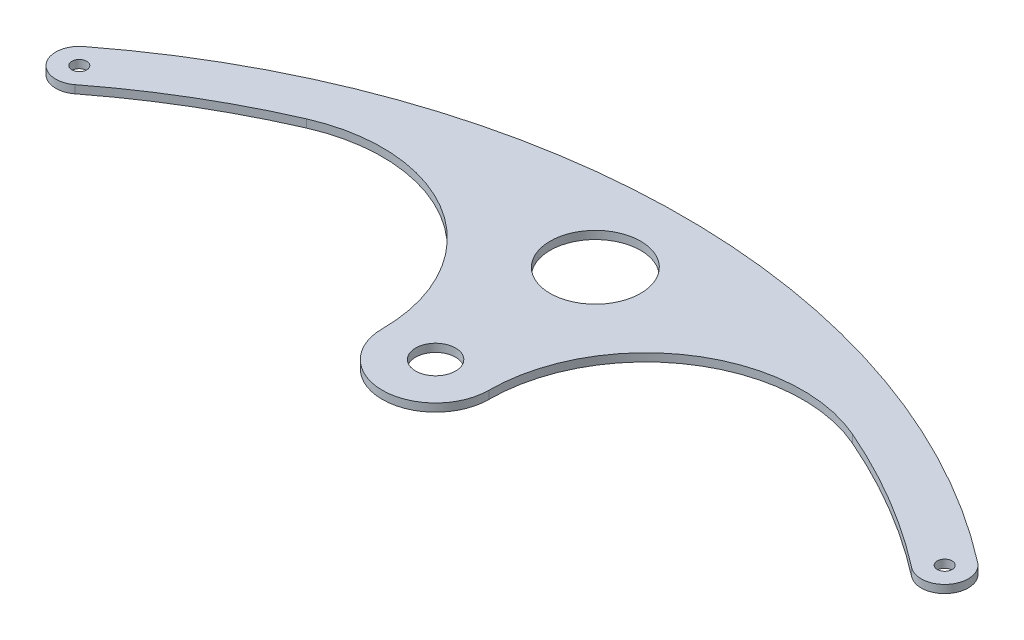
SolidWorks part; units mm, degrees
ref_plane "Front Plane" through (0, 0, 0) normal (0, 0, 1) x (1, 0, 0)
ref_plane "Top Plane" through (0, 0, 0) normal (0, 1, 0) x (1, 0, 0)
ref_plane "Right Plane" through (0, 0, 0) normal (1, 0, 0) x (0, 0, -1)
sketch "Sketch1" plane through (0, 0, 0) normal (0, 1, 0) x (1, 0, 0)
  line L0 (3.048, 4.191) -> (3.048, -6.604) construction
  line L1 (0, 0) -> (206.375, 0) construction
  line L2 (103.1875, 0) -> (103.1875, 50.9033) construction
  line L3 (47.625, 0) -> (47.625, 19.05) construction
  line L4 (60.3023, -7.112) -> (162.9473, -7.112) construction
  line L5 (60.3023, -18.2245) -> (162.9473, -18.2245) construction
  line L6 (103.1875, 0) -> (103.1875, -18.2245) construction
  circle A0 centre (0, 0) radius 1.778
  circle A1 centre (206.375, 0) radius 1.778
  arc A3 (-3.435, 4.439) -> (3.435, -4.439) centre (0, 0) ccw
  arc A4 (209.81, 4.439) -> (202.94, -4.439) centre (206.375, 0) cw
  arc A5 (202.94, -4.439) -> (168.2637, 16.0946) centre (103.1875, -133.35) ccw
  arc A6 (209.81, 4.439) -> (-3.435, 4.439) centre (103.1875, -133.35) ccw
  circle A7 centre (103.1875, -18.2245) radius 4.7625
  arc A8 (90.4875, -18.2245) -> (115.8875, -18.2245) centre (103.1875, -18.2245) ccw
  arc A9 (90.4875, -18.2245) -> (38.1113, 16.0946) centre (53.0557, -18.2245) ccw
  arc A10 (115.8875, -18.2245) -> (168.2637, 16.0946) centre (153.3193, -18.2245) cw
  arc A11 (38.1113, 16.0946) -> (3.435, -4.439) centre (103.1875, -133.35) ccw
  circle A12 centre (103.1875, 19.8755) radius 10.795
  dimension "D2" = 3.556
  dimension "D3" = 3.556
  dimension "D4" = 18.2245
  dimension "D12" = 9.525
  dimension "D13" = 25.4
  dimension "D14" = 74.8636
  dimension "D15" = 21.59
  dimension "D1" = 206.375
  dimension "D5" = 3.048
  dimension "D6" = 6.604
  dimension "D7" = 47.625
  dimension "D8" = 19.05
  dimension "D9" = 133.35
  dimension "D10" = 7.112
  dimension "D11" = 11.1125
  dimension "D16" = 38.1
extrude "Boss-Extrude1" add sketch "Sketch1" along normal blind 1.905
